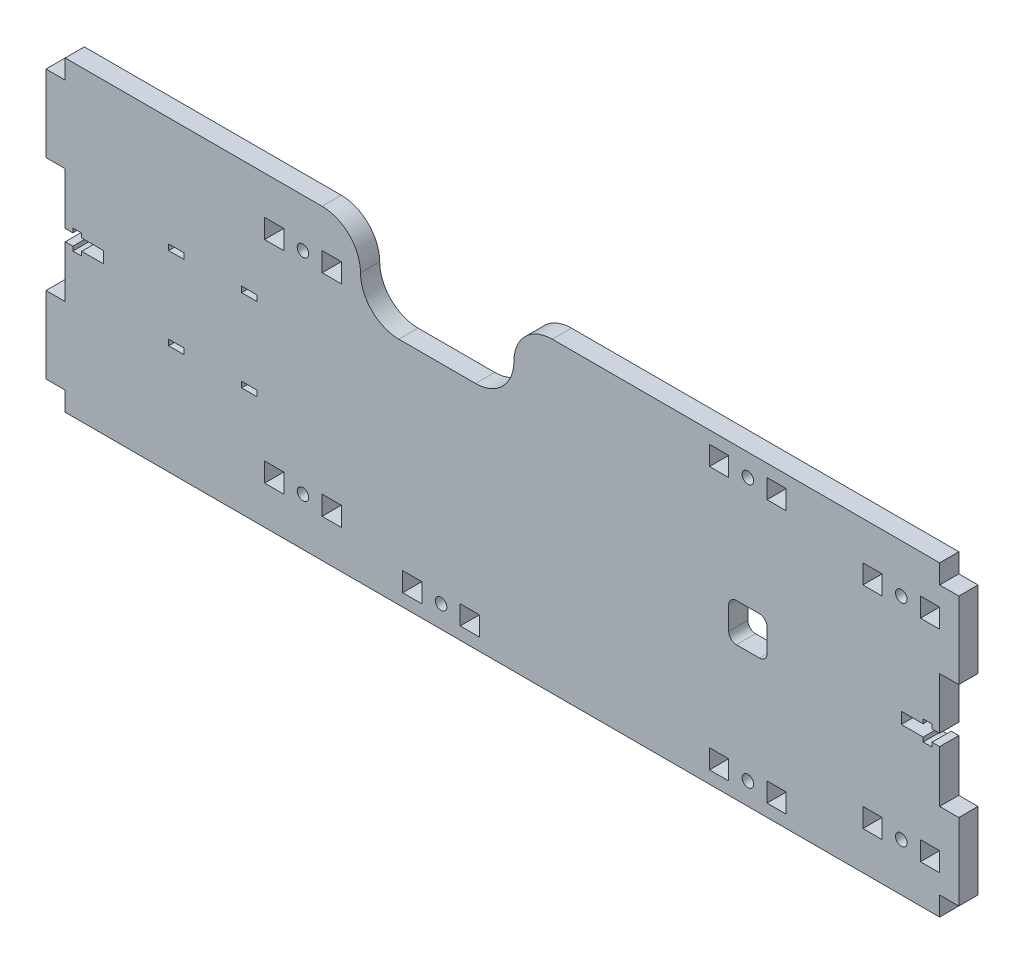
SolidWorks part; units mm, degrees
ref_plane "Plan de face" through (0, 0, 0) normal (0, 0, 1) x (1, 0, 0)
ref_plane "Plan de dessus" through (0, 0, 0) normal (0, 1, 0) x (1, 0, 0)
ref_plane "Plan de droite" through (0, 0, 0) normal (1, 0, 0) x (0, 0, -1)
sketch "Esquisse1" plane through (0, 0, 0) normal (0, 0, 1) x (1, 0, 0)
  line L0 (0, 35) -> (0, 15)
  line L1 (0, 15) -> (5, 15)
  line L2 (5, 15) -> (5, 1.5)
  line L3 (5, 1.5) -> (7, 1.5)
  line L4 (7, 1.5) -> (7, 2.6)
  line L5 (7, 2.6) -> (9.3, 2.6)
  line L6 (9.3, 2.6) -> (9.3, 1.5)
  line L7 (9.3, 1.5) -> (15, 1.5)
  line L8 (15, 1.5) -> (15, -1.5)
  line L9 (15, -1.5) -> (9.3, -1.5)
  line L10 (9.3, -1.5) -> (9.3, -2.6)
  line L11 (9.3, -2.6) -> (7, -2.6)
  line L12 (7, -2.6) -> (7, -1.5)
  line L13 (7, -1.5) -> (5, -1.5)
  line L14 (5, -1.5) -> (5, -15)
  line L15 (5, -15) -> (0, -15)
  line L16 (0, -15) -> (0, -35)
  line L17 (0, 35) -> (5, 35)
  line L18 (5, 35) -> (5, 40)
  line L19 (119, -36.5) -> (119, 67.7368) construction
  line L20 (0, 0) -> (119, 0) construction
  line L21 (238, 35) -> (238, 15)
  line L22 (238, 15) -> (233, 15)
  line L23 (233, 15) -> (233, 1.5)
  line L24 (233, 1.5) -> (231, 1.5)
  line L25 (231, 1.5) -> (231, 2.6)
  line L26 (231, 2.6) -> (228.7, 2.6)
  line L27 (228.7, 2.6) -> (228.7, 1.5)
  line L28 (228.7, 1.5) -> (223, 1.5)
  line L29 (223, 1.5) -> (223, -1.5)
  line L30 (223, -1.5) -> (228.7, -1.5)
  line L31 (228.7, -1.5) -> (228.7, -2.6)
  line L32 (228.7, -2.6) -> (231, -2.6)
  line L33 (231, -2.6) -> (231, -1.5)
  line L34 (231, -1.5) -> (233, -1.5)
  line L35 (233, -1.5) -> (233, -15)
  line L36 (233, -15) -> (238, -15)
  line L37 (238, -15) -> (238, -35)
  line L38 (5, 40) -> (233, 40)
  line L39 (233, 40) -> (233, 35)
  line L40 (233, 35) -> (238, 35)
  line L41 (238, -35) -> (233, -35)
  line L42 (233, -35) -> (233, -40)
  line L43 (233, -40) -> (5, -40)
  line L44 (5, -40) -> (5, -35)
  line L45 (5, -35) -> (0, -35)
  line L46 (32, -11.5) -> (32, -10)
  line L47 (32, 11.5) -> (36, 11.5)
  line L48 (32, 11.5) -> (32, 10)
  line L49 (32, 10) -> (36, 10)
  line L50 (36, 11.5) -> (36, 10)
  line L51 (51, 11.5) -> (55, 11.5)
  line L52 (51, 11.5) -> (51, 10)
  line L53 (51, 10) -> (55, 10)
  line L54 (55, 11.5) -> (55, 10)
  line L55 (32, -10) -> (36, -10)
  line L56 (36, -11.5) -> (36, -10)
  line L57 (32, -11.5) -> (36, -11.5)
  line L58 (51, -11.5) -> (51, -10)
  line L59 (51, -10) -> (55, -10)
  line L60 (55, -11.5) -> (55, -10)
  line L61 (51, -11.5) -> (55, -11.5)
  point P31 (119, 33.5)
  line B0 (218, 27.5) -> (228, 27.5) construction
  line B1 (218, 30) -> (213, 30)
  line B2 (218, 30) -> (218, 25)
  line B3 (218, 25) -> (213, 25)
  line B4 (213, 30) -> (213, 25)
  line B5 (228, 30) -> (233, 30)
  line B6 (228, 30) -> (228, 25)
  line B7 (228, 25) -> (233, 25)
  line B8 (233, 30) -> (233, 25)
  line B9 (223, 27.5) -> (223, 34.4724) construction
  circle B10 centre (223, 27.5) radius 1.5
  line B11 (218, -27.5) -> (228, -27.5) construction
  line B12 (218, -25) -> (213, -25)
  line B13 (218, -25) -> (218, -30)
  line B14 (218, -30) -> (213, -30)
  line B15 (213, -25) -> (213, -30)
  line B16 (228, -25) -> (233, -25)
  line B17 (228, -25) -> (228, -30)
  line B18 (228, -30) -> (233, -30)
  line B19 (233, -25) -> (233, -30)
  line B20 (223, -27.5) -> (223, -20.5276) construction
  circle B21 centre (223, -27.5) radius 1.5
  line B22 (62, -25) -> (57, -25)
  line B23 (62, -25) -> (62, -30)
  line B24 (62, -30) -> (57, -30)
  line B25 (57, -25) -> (57, -30)
  line B26 (72, -25) -> (77, -25)
  line B27 (72, -25) -> (72, -30)
  line B28 (72, -30) -> (77, -30)
  line B29 (77, -25) -> (77, -30)
  circle B30 centre (67, -27.5) radius 1.5
  line B31 (62, 27.5) -> (72, 27.5) construction
  line B32 (62, 30) -> (57, 30)
  line B33 (62, 30) -> (62, 25)
  line B34 (62, 25) -> (57, 25)
  line B35 (57, 30) -> (57, 25)
  line B36 (72, 30) -> (77, 30)
  line B37 (72, 30) -> (72, 25)
  line B38 (72, 25) -> (77, 25)
  line B39 (77, 30) -> (77, 25)
  line B40 (67, 27.5) -> (67, 34.4724) construction
  circle B41 centre (67, 27.5) radius 1.5
  line B42 (178, -31.75) -> (173, -31.75)
  line B43 (178, -31.75) -> (178, -36.75)
  line B44 (178, -36.75) -> (173, -36.75)
  line B45 (173, -31.75) -> (173, -36.75)
  line B46 (188, -31.75) -> (193, -31.75)
  line B47 (188, -31.75) -> (188, -36.75)
  line B48 (188, -36.75) -> (193, -36.75)
  line B49 (193, -31.75) -> (193, -36.75)
  line B50 (183, -34.25) -> (183, -27.2776) construction
  circle B51 centre (183, -34.25) radius 1.5
  line B52 (178, 31.75) -> (173, 31.75)
  line B53 (178, 31.75) -> (178, 36.75)
  line B54 (178, 36.75) -> (173, 36.75)
  line B55 (173, 31.75) -> (173, 36.75)
  line B56 (188, 31.75) -> (193, 31.75)
  line B57 (188, 31.75) -> (188, 36.75)
  line B58 (188, 36.75) -> (193, 36.75)
  line B59 (193, 31.75) -> (193, 36.75)
  circle B60 centre (183, 34.25) radius 1.5
  line B61 (98, 31.75) -> (93, 31.75)
  line B62 (98, 31.75) -> (98, 36.75)
  line B63 (98, 36.75) -> (93, 36.75)
  line B64 (93, 31.75) -> (93, 36.75)
  line B65 (108, 31.75) -> (113, 31.75)
  line B66 (108, 31.75) -> (108, 36.75)
  line B67 (108, 36.75) -> (113, 36.75)
  line B68 (113, 31.75) -> (113, 36.75)
  circle B69 centre (103, 34.25) radius 1.5
  line B70 (98, -31.75) -> (93, -31.75)
  line B71 (98, -31.75) -> (98, -36.75)
  line B72 (98, -36.75) -> (93, -36.75)
  line B73 (93, -31.75) -> (93, -36.75)
  line B74 (108, -31.75) -> (113, -31.75)
  line B75 (108, -31.75) -> (108, -36.75)
  line B76 (108, -36.75) -> (113, -36.75)
  line B77 (113, -31.75) -> (113, -36.75)
  line B78 (103, -34.25) -> (103, -27.2776) construction
  circle B79 centre (103, -34.25) radius 1.5
  dimension "D2" = 3
  dimension "D3" = 5.2
  dimension "D4" = 2.3
  dimension "D5" = 5
  dimension "D6" = 2
  dimension "D7" = 10
  dimension "D8" = 30
  dimension "D9" = 238
  dimension "D10" = 20
  dimension "D11" = 20
  dimension "D12" = 80
  dimension "D13" = 5
  dimension "D14" = 50
  dimension "D15" = 156
  dimension "D16" = 4
  dimension "D17" = 1.5
  dimension "D18" = 15
  dimension "D19" = 2
  dimension "D20" = 10
  dimension "D21" = 63.5
  dimension "D22" = 40
  dimension "D23" = 63.5
  dimension "D24" = 80
sketch_block_instance "Trou M3 plots 5mm-8"
sketch_block "Trou M3 plots 5mm" parameters "D2"=3, "D1"=5, "D3"=5, "D4"=10
sketch_block_instance "Trou M3 plots 5mm-9"
sketch_block_instance "Trou M3 plots 5mm-10"
sketch_block_instance "Trou M3 plots 5mm-11"
sketch_block_instance "Trou M3 plots 5mm-12"
sketch_block_instance "Trou M3 plots 5mm-13"
sketch_block_instance "Trou M3 plots 5mm-14"
sketch_block_instance "Trou M3 plots 5mm-15"
extrude "Boss.-Extru.1" add sketch "Esquisse1" along normal blind 5
sketch "Sketch1" plane through (0, 0, 0) normal (0, 0, -1) x (-1, 0, 0)
  line L6 (-233, 40) -> (-5, 40) construction
  line L7 (-82, 40) -> (-122, 40)
  line L8 (-82, 40) -> (-82, 20)
  line L9 (-82, 20) -> (-122, 20)
  line L10 (-122, 40) -> (-122, 20)
  line L11 (-77, 25) -> (-77, 30) construction
  line L12 (-236.561, 0) -> (-128.3605, 0) construction
  line L13 (-188, 5) -> (-178, 5)
  line L14 (-188, 5) -> (-188, -5)
  line L15 (-188, -5) -> (-178, -5)
  line L16 (-178, 5) -> (-178, -5)
  line L17 (-233, 1.5) -> (-233, 15) construction
  point P8 (-77, 27.5)
  point P16 (-188, 0)
  dimension "D1" = 20
  dimension "D2" = 40
  dimension "D3" = 5
  dimension "D4" = 10
  dimension "D5" = 10
  dimension "D6" = 45
extrude "Cut-Extrude1" cut sketch "Sketch1" against normal blind 10
fillet "Fillet2" radius 10 4 edges at (122, 40, 2.5) (82, 40, 2.5) (122, 20, 2.5) (82, 20, 2.5)
fillet "Fillet3" radius 2 4 edges at (178, -5, 2.5) (178, 5, 2.5) (188, 5, 2.5) (188, -5, 2.5)
